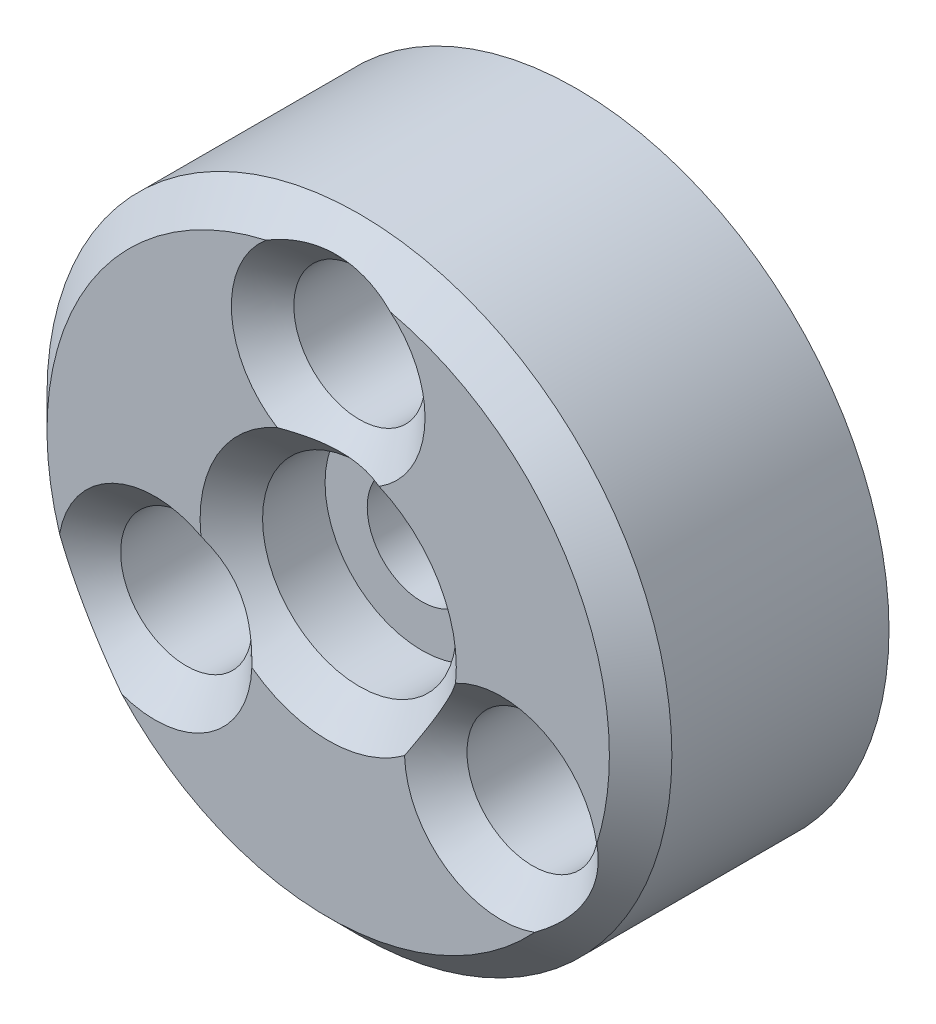
SolidWorks part; units mm, degrees
ref_plane "Front Plane" through (0, 0, 0) normal (0, 0, 1) x (1, 0, 0)
ref_plane "Top Plane" through (0, 0, 0) normal (0, 1, 0) x (1, 0, 0)
ref_plane "Right Plane" through (0, 0, 0) normal (1, 0, 0) x (0, 0, -1)
sketch "Sketch1" plane through (0, 0, 0) normal (0, 0, 1) x (1, 0, 0)
  line L0 (0, 0) -> (6, 0) construction
  circle A0 centre (0, 0) radius 10
  circle A1 centre (6, 0) radius 2.1
  circle A2 centre (0, 0) radius 1.75
  circle A3 centre (0, -6) radius 2.1
  circle A4 centre (-6, 0) radius 2.1
  circle A5 centre (0, 6) radius 2.1
  point P6 (-1.5916, 7.1105)
  point P7 (0, 0)
  point P15 (0, 0)
  dimension "D1" = 4.2
  dimension "D3" = 3.5
  dimension "D4" = 20
  dimension "D2" = 6
  dimension "D5" = 4
extrude "Boss-Extrude1" add sketch "Sketch1" along normal mid plane 8
sketch "Sketch2" plane through (0, 0, -4) normal (0, 0, -1) x (-1, 0, 0)
  circle A0 centre (0, 0) radius 9.05
  dimension "D1" = 18.1
extrude "Cut-Extrude1" cut sketch "Sketch2" against normal blind 2.9
chamfer "Chamfer1" distance 1 angle 45 1 edges at (-9.05, 0, -4)
sketch "Sketch3" plane through (0, 0, -1.1) normal (0, 0, -1) x (-1, 0, 0)
  circle A0 centre (-6, 0) radius 2.1 construction
  circle A1 centre (0, -6) radius 2.1 construction
  circle A2 centre (6, 0) radius 2.1 construction
  circle A3 centre (0, 6) radius 2.1 construction
  circle A4 centre (-6, 0) radius 2.1
  circle A5 centre (0, -6) radius 2.1
  circle A6 centre (6, 0) radius 2.1
  circle A7 centre (0, 6) radius 2.1
extrude "Boss-Extrude2" add sketch "Sketch3" against normal up to surface (5.1 mm away) and the other way blind 2.9 up to face at (-3.9, 0, 4)
chamfer "Chamfer2" distance 0.6 angle 45 4 edges at (3.9, 0, -4) (-2.1, -6, -4) (-8.1, 0, -4) (-2.1, 6, -4)
sketch "Sketch4" plane through (0, 0, 4) normal (0, 0, 1) x (1, 0, 0)
  circle A0 centre (0, 0) radius 3.1
  dimension "D1" = 6.2
extrude "Cut-Extrude2" cut sketch "Sketch4" against normal blind 3
sketch "Sketch5" plane through (0, 0, 4) normal (0, 0, 1) x (1, 0, 0)
  circle A0 centre (0, 6.4) radius 2.1
  circle A1 centre (5.5426, -3.2) radius 2.1
  circle A2 centre (-5.5426, -3.2) radius 2.1
  point P2 (-6.9148, -4.5768)
  point P4 (0, 0)
  point P10 (0, 0)
  dimension "D1" = 4.2
  dimension "D2" = 6.4
  dimension "D3" = 3
extrude "Cut-Extrude3" cut sketch "Sketch5" against normal blind 4
sketch "Sketch6" plane through (0, 0, 0) normal (0, 0, 1) x (1, 0, 0)
  circle A0 centre (0, 6.4) radius 0.625
  dimension "D1" = 1.25
extrude "Cut-Extrude4" cut sketch "Sketch6" against normal through all
pattern_circular "CirPattern1" count 3 over 360 about axis through (0, 0, 4) along (0, 0, -1) of "Cut-Extrude4"
chamfer "Chamfer3" distance 1 angle 45 3 edges at (-5.8551, -2.6587, 0) (5.2301, -3.7413, 0) (0.625, 6.4, 0)
chamfer "Chamfer4" distance 1 angle 45 5 edges at (10, 0, 4) (-3.4426, -3.2, 4) (7.6426, -3.2, 4) (2.1, 6.4, 4) (3.1, 0, 4)
